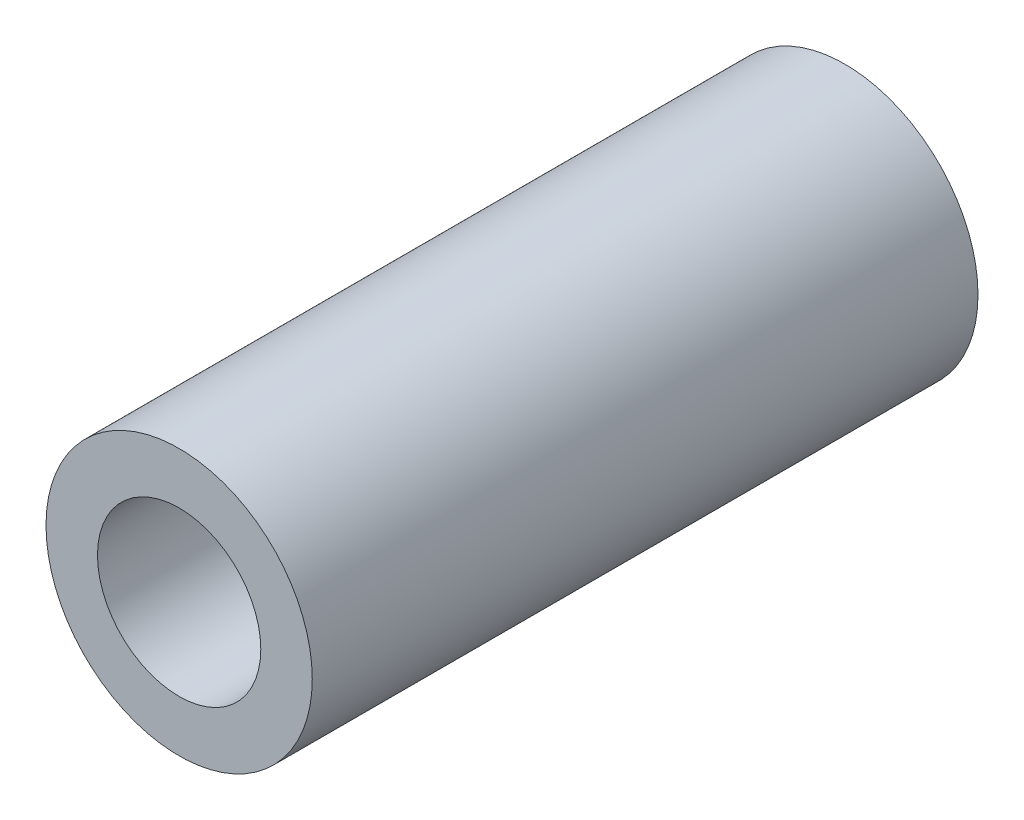
SolidWorks part; units mm, degrees
material "Nylon 6/10"
ref_plane "Front Plane" through (0, 0, 0) normal (0, 0, 1) x (1, 0, 0)
ref_plane "Top Plane" through (0, 0, 0) normal (0, 1, 0) x (1, 0, 0)
ref_plane "Right Plane" through (0, 0, 0) normal (1, 0, 0) x (0, 0, -1)
sketch "Sketch1" plane through (0, 0, 0) normal (0, 0, 1) x (1, 0, 0)
  circle A0 centre (0, 0) radius 2.3813
  circle A1 centre (0, 0) radius 1.4605
  dimension "OD" = 4.7625
  dimension "ID" = 2.921
extrude "Extrude1" add sketch "Sketch1" along normal mid plane 11.9075
sketch "Sketch2" plane through (0, 0, 0) normal (1, 0, 0) x (0, 0, -1)
  line L0 (-5.9538, -1.4605) -> (5.9538, -1.4605) construction
  line L3 (5.9538, 1.4605) -> (-5.9538, 1.4605) construction
  line L5 (-5.9538, -1.4605) -> (5.9538, -1.4605)
  line L6 (5.9538, 1.4605) -> (-5.9538, 1.4605)
sketch "Sketch4" plane through (0, 0, 5.9538) normal (0, 0, 1) x (1, 0, 0)
  line L0 (0, 0) -> (-1.0327, 1.0327)
  line L1 (0, -2.6194) -> (0, 2.6194) construction
  circle A0 centre (0, 0) radius 1.4605 construction
  dimension "D1" = 45
